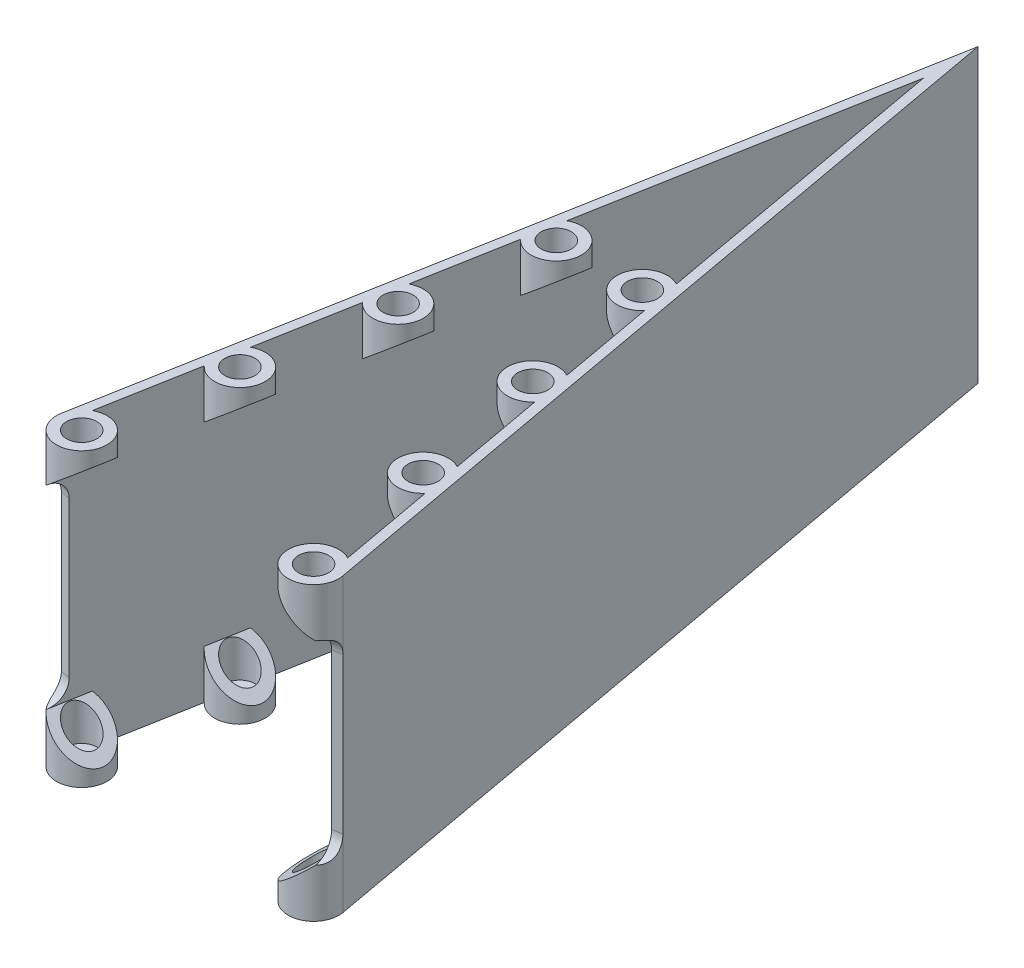
SolidWorks part; units mm, degrees
ref_plane "Front Plane" through (0, 0, 0) normal (0, 0, 1) x (1, 0, 0)
ref_plane "Top Plane" through (0, 0, 0) normal (0, 1, 0) x (1, 0, 0)
ref_plane "Right Plane" through (0, 0, 0) normal (1, 0, 0) x (0, 0, -1)
sketch "Sketch1" plane through (0, 0, 0) normal (0, 1, 0) x (1, 0, 0)
  line L0 (-13.5, 0) -> (13.5, 0) construction
  line L1 (-13.5, 0) -> (0, 74.399)
  line L2 (0, 74.399) -> (13.5, 0)
  line L3 (13.5, 0) -> (14.4839, 0.1785)
  line L4 (14.4839, 0.1785) -> (0, 80)
  line L5 (0, 80) -> (-14.4839, 0.1785)
  line L6 (-14.4839, 0.1785) -> (-13.5, 0)
  point P2 (0, 0)
  dimension "D1" = 90
  dimension "D2" = 90
  dimension "D4" = 1
  dimension "D5" = 27
  dimension "D3" = 80
extrude "Boss-Extrude1" add sketch "Sketch1" along normal blind 30
sketch "Sketch2" plane through (0, 0, 0) normal (0, 1, 0) x (1, 0, 0)
  line L0 (0, -1000) -> (0, 49000) construction
  line L1 (0, 74.399) -> (13.5, 0) construction
  line L2 (0, 74.399) -> (13.5, 0) construction
  line L3 (11.9257, -0.2857) -> (13.5, 0) construction
  line L4 (13.5, 0) -> (14.4839, 0.1785) construction
  line L5 (14.4839, 0.1785) -> (0, 80) construction
  line L6 (14.4839, 0.1785) -> (0, 80) construction
  circle A0 centre (11.9257, -0.2857) radius 2.6
  circle A1 centre (11.9257, -0.2857) radius 1.55
  circle A22 centre (9.4262, 13.4894) radius 1.55
  circle A23 centre (9.4262, 13.4894) radius 2.6
  circle A24 centre (6.9266, 27.2645) radius 1.55
  circle A25 centre (6.9266, 27.2645) radius 2.6
  circle A26 centre (4.4271, 41.0395) radius 1.55
  circle A27 centre (4.4271, 41.0395) radius 2.6
  circle A28 centre (-11.9257, -0.2857) radius 2.6
  circle A29 centre (-11.9257, -0.2857) radius 1.55
  circle A30 centre (-9.4262, 13.4894) radius 2.6
  circle A31 centre (-9.4262, 13.4894) radius 1.55
  circle A32 centre (-6.9266, 27.2645) radius 2.6
  circle A33 centre (-6.9266, 27.2645) radius 1.55
  circle A34 centre (-4.4271, 41.0395) radius 2.6
  circle A35 centre (-4.4271, 41.0395) radius 1.55
  dimension "D1" = 5.2
  dimension "D2" = 3.1
  dimension "D4" = 14
  dimension "D3" = 4
extrude "Boss-Extrude3" add sketch "Sketch2" along normal blind 5
sketch "Sketch4" plane through (0.4303, 0, 2.3715) normal (0.1785, 0, 0.9839) x (0.9839, 0, -0.1785)
  line L0 (9.0831, 5) -> (9.0831, 0) construction
  line L1 (14.2831, 5) -> (9.0831, 5) construction
  line L2 (13.2831, 30) -> (13.2831, 0) construction
  line L3 (9.0831, 5) -> (9.0831, 0) construction
  line L4 (14.2831, 5) -> (9.0831, 5) construction
  line L5 (13.2831, 30) -> (13.2831, 0) construction
  line L6 (13.2831, 5) -> (9.0831, 1.4758)
  line L7 (13.2831, 5) -> (9.0831, 5)
  line L8 (9.0831, 5) -> (9.0831, 1.4758)
  dimension "D1" = 40
extrude "Cut-Extrude1" cut sketch "Sketch4" against normal up to surface and the other way through all contours L7 L8 L6 up to face at (-8.6266, 5.5556, -26.8574)
sketch "Sketch5" plane through (-0.4303, 0, 2.3715) normal (-0.1785, 0, 0.9839) x (0.9839, 0, 0.1785)
  line L0 (-9.0831, 0) -> (-9.0831, 5) construction
  line L1 (-9.0831, 5) -> (-14.2831, 5) construction
  line L2 (-13.2831, 30) -> (-13.2831, 0) construction
  line L3 (-9.0831, 0) -> (-9.0831, 5) construction
  line L4 (-9.0831, 5) -> (-14.2831, 5) construction
  line L5 (-13.2831, 30) -> (-13.2831, 0) construction
  line L6 (-13.2831, 5) -> (-9.0831, 1.4758)
  line L7 (-13.2831, 5) -> (-9.0831, 5)
  line L8 (-9.0831, 5) -> (-9.0831, 1.4758)
  dimension "D1" = 40
extrude "Cut-Extrude2" cut sketch "Sketch5" against normal up to surface and the other way through all contours L8 L7 L6 up to face at (8.6266, 5.5556, -26.8574)
ref_plane "Plane1" through (0, 15, 0) normal (0, 1, 0) x (1, 0, 0)
mirror "Mirror2" about plane through (0, 15, 0) normal (0, 1, 0) of "Cut-Extrude2", "Cut-Extrude1", "Boss-Extrude3"
fillet "Fillet1" radius 2 4 edges at (13.992, 5, -0.0893) (13.992, 25, -0.0893) (-13.992, 25, -0.0893) (-13.992, 5, -0.0893)
sketch "Sketch6" plane through (0, 0, 0) normal (0, -1, 0) x (1, 0, 0)
  arc A0 (6.3673, -39.3087) -> (5.6355, -43.3416) centre (4.4271, -41.0395) ccw construction
  arc A1 (14.4839, -0.1785) -> (13.1341, -2.0165) centre (11.9257, 0.2857) ccw construction
  arc A2 (-5.6355, -43.3416) -> (-6.3673, -39.3087) centre (-4.4271, -41.0395) ccw construction
  arc A3 (-8.135, -29.5666) -> (-8.8668, -25.5337) centre (-6.9266, -27.2645) ccw construction
  arc A4 (8.8668, -25.5337) -> (8.135, -29.5666) centre (6.9266, -27.2645) ccw construction
  arc A5 (11.3664, -11.7586) -> (10.6346, -15.7915) centre (9.4262, -13.4894) ccw construction
  arc A6 (-10.6346, -15.7915) -> (-11.3664, -11.7586) centre (-9.4262, -13.4894) ccw construction
  arc A7 (-13.1341, -2.0165) -> (-14.4839, -0.1785) centre (-11.9257, 0.2857) ccw construction
  arc A8 (6.3673, -39.3087) -> (5.6355, -43.3416) centre (4.4271, -41.0395) ccw
  arc A9 (-5.6355, -43.3416) -> (-6.3673, -39.3087) centre (-4.4271, -41.0395) ccw
  arc A10 (-8.135, -29.5666) -> (-8.8668, -25.5337) centre (-6.9266, -27.2645) ccw
  arc A11 (14.4839, -0.1785) -> (13.1341, -2.0165) centre (11.9257, 0.2857) ccw
  arc A12 (8.8668, -25.5337) -> (8.135, -29.5666) centre (6.9266, -27.2645) ccw
  arc A13 (11.3664, -11.7586) -> (10.6346, -15.7915) centre (9.4262, -13.4894) ccw
  arc A14 (-10.6346, -15.7915) -> (-11.3664, -11.7586) centre (-9.4262, -13.4894) ccw
  arc A15 (-13.1341, -2.0165) -> (-14.4839, -0.1785) centre (-11.9257, 0.2857) ccw
  circle A16 centre (-11.9257, 0.2857) radius 2.6
  circle A17 centre (-9.4262, -13.4894) radius 2.6
  circle A18 centre (-6.9266, -27.2645) radius 2.6
  circle A19 centre (-4.4271, -41.0395) radius 2.6
  circle A28 centre (11.9257, 0.2857) radius 2.6
  circle A29 centre (4.4271, -41.0395) radius 2.6
  circle A30 centre (6.9266, -27.2645) radius 2.6
  circle A31 centre (9.4262, -13.4894) radius 2.6
extrude "Boss-Extrude4" add sketch "Sketch6" against normal blind 1
equation "\"D2@Sketch1\"=\"D1@Sketch1\""
